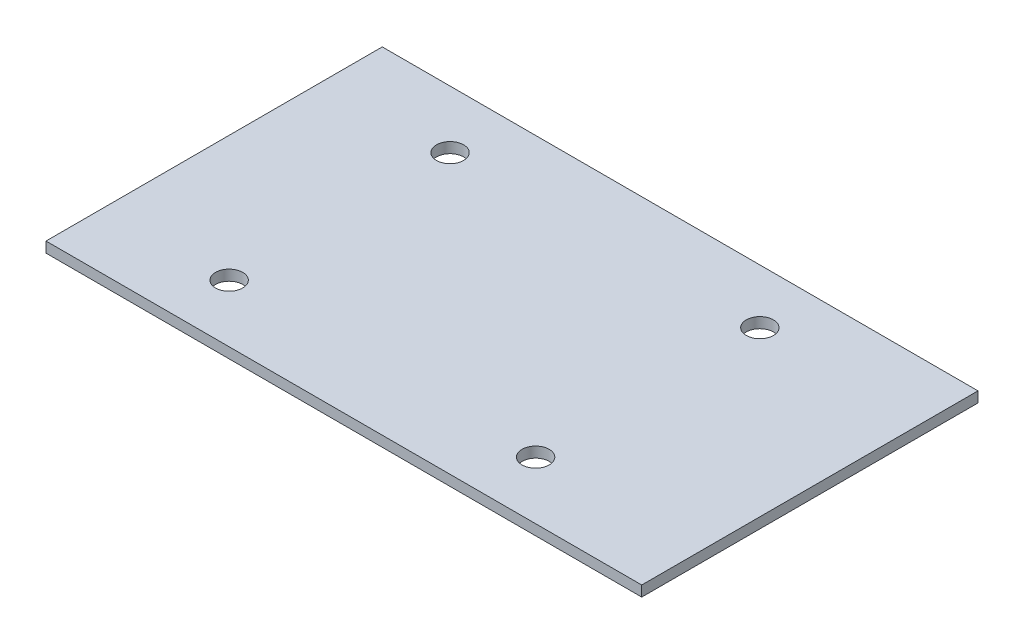
SolidWorks part; units mm, degrees
material "Cast Alloy Steel"
ref_plane "Front Plane" through (0, 0, 0) normal (0, 0, 1) x (1, 0, 0)
ref_plane "Top Plane" through (0, 0, 0) normal (0, 1, 0) x (1, 0, 0)
ref_plane "Right Plane" through (0, 0, 0) normal (1, 0, 0) x (0, 0, -1)
sketch "Sketch1" plane through (0, 0, 0) normal (0, 1, 0) x (1, 0, 0)
  line L1 (90, 50.8) -> (-90, 50.8)
  line L2 (90, 50.8) -> (90, -50.8)
  line L3 (90, -50.8) -> (-90, -50.8)
  line L4 (-90, 50.8) -> (-90, -50.8)
  line L5 (90, 50.8) -> (-90, -50.8) construction
  line L6 (90, -50.8) -> (-90, 50.8) construction
  circle A0 centre (-52.0875, 33.3735) radius 4.1
  circle A1 centre (40.5125, 34.3735) radius 4.1
  circle A2 centre (40.5125, -33.3735) radius 4.1
  circle A3 centre (-52.0875, -33.3735) radius 4.1
  point P0 (0, 0)
  dimension "D3" = 8.2
  dimension "D1" = 101.6
  dimension "D2" = 180
extrude "Boss-Extrude1" add sketch "Sketch1" along normal blind 3.175
